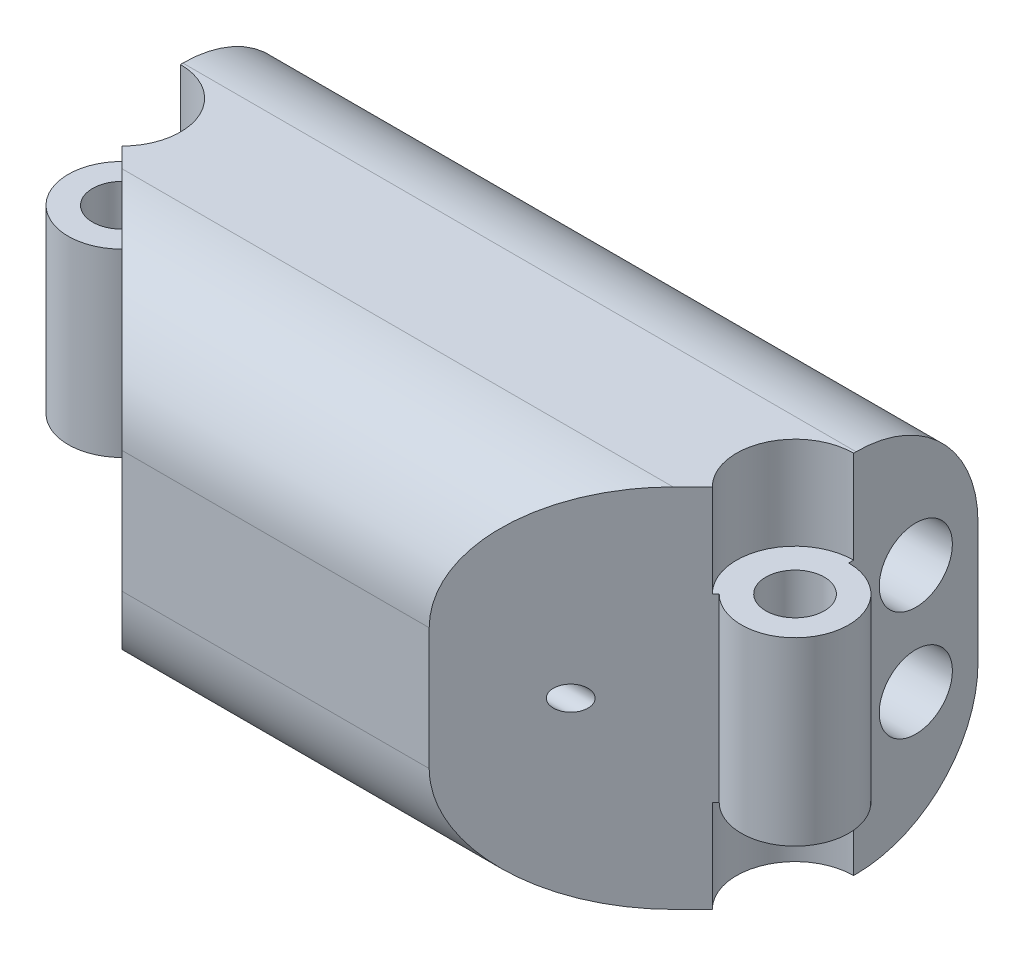
SolidWorks part; units mm, degrees
ref_plane "Front Plane" through (0, 0, 0) normal (1, 0, 0) x (0, 1, 0)
ref_plane "Top Plane" through (0, 0, 0) normal (0, 0, 1) x (0, 1, 0)
ref_plane "Right Plane" through (0, 0, 0) normal (0, 1, 0) x (-1, 0, 0)
sketch "Sketch1" plane through (0, 0, 0) normal (0, 1, 0) x (-1, 0, 0)
  line L1 (-6.3, 7.5) -> (6.3, 7.5)
  line L4 (13.8, -7.5) -> (-13.8, -7.5)
  line L6 (-13.8, -7.5) -> (-13.8, 0)
  line L7 (-13.8, 7.5) -> (-6.3, 7.5) construction
  line L8 (6.3, 7.5) -> (13.8, 7.5) construction
  line L9 (6.3, 7.5) -> (13.8, 0)
  line L10 (-13.8, 7.5) -> (13.8, -7.5) construction
  line L11 (-13.8, 0) -> (-6.3, 7.5)
  line L12 (-13.8, 7.5) -> (-13.8, 0) construction
  line L13 (13.8, 0) -> (13.8, -7.5)
  line L14 (13.8, 0) -> (13.8, 7.5) construction
  arc A4 (12.1029, 1.6971) -> (13.8, -2.4) centre (13.8, 0) ccw
  circle A5 centre (13.8, 0) radius 1.2 construction
  circle A6 centre (13.8, 0) radius 2.2 construction
  arc A7 (-13.8, -2.4) -> (-12.1029, 1.6971) centre (-13.8, 0) ccw
  dimension "D3" = 1
  dimension "D4" = 0.2
  dimension "D5" = 4.8
  dimension "D2" = 2.4
  dimension "D1" = 15
extrude "Boss-Extrude1" add sketch "Sketch1" along normal blind 7.5 and the other way blind 7.5 contours L1 L4 region at (0, 0, -0.7982)
sketch "Sketch5" plane through (13.8, 0, 0) normal (1, 0, 0) x (0, 1, 0)
  line L0 (0, -2.4) -> (0, -7.5) construction
  line L1 (-2.25, -4.95) -> (2.25, -4.95) construction
  line L2 (-7.5, -2.4) -> (7.5, -2.4) construction
  line L3 (-7.5, -7.5) -> (7.5, -7.5) construction
  circle A0 centre (-2.25, -4.95) radius 1.5
  circle A1 centre (2.25, -4.95) radius 1.5
  point P4 (0.75, -4.95)
  point P7 (0, -4.95)
  point P8 (-0.75, -4.95)
  point P9 (0, -4.95)
  dimension "D1" = 3
  dimension "D2" = 1.5
  dimension "D3" = 0
extrude "Cut-Extrude3" cut sketch "Sketch5" against normal up to next
fillet "Fillet1" radius 5 2 edges at (0, -7.5, -7.5) (0, 7.5, -7.5)
sketch "Sketch3" plane through (0, 0, 0) normal (1, 0, 0) x (0, 1, 0)
  line L0 (-7.5, 4.5985) -> (7.5, 4.5985) construction
  line L3 (-7.5, 1.6971) -> (-7.5, 7.5) construction
  line L4 (7.5, 1.6971) -> (7.5, 7.5) construction
  circle A0 centre (0, 4.5985) radius 0.5
extrude "Cut-Extrude2" cut sketch "Sketch3" against normal up to next and the other way up to next
fillet "Fillet2" radius 5 2 edges at (0, 7.5, 7.5) (0, -7.5, 7.5)
sketch "Sketch6" plane through (0, 0, 0) normal (0, 1, 0) x (-1, 0, 0)
  line L4 (0, 7.5) -> (0, -7.5) construction
  line L5 (-6.3, 7.5) -> (6.3, 7.5) construction
  line L6 (13.8, -7.5) -> (-13.8, -7.5) construction
  line L7 (-12.1029, 1.6971) -> (-12.2444, 1.5556)
  line L9 (-13.8, -2.4) -> (-13.8, -2.2)
  line L10 (-12.1029, 1.6971) -> (-11.3, 2.5) construction
  line L11 (13.8, -2.4) -> (13.8, -2.2)
  line L12 (12.1029, 1.6971) -> (12.2444, 1.5556)
  arc A6 (-12.2444, 1.5556) -> (-13.8, -2.2) centre (-13.8, 0) ccw
  circle A7 centre (-13.8, 0) radius 1.2
  arc A8 (-13.8, -2.4) -> (-12.1029, 1.6971) centre (-13.8, 0) ccw
  arc A9 (-13.8, -2.4) -> (-12.1029, 1.6971) centre (-13.8, 0) ccw construction
  arc A10 (13.8, -2.4) -> (12.1029, 1.6971) centre (13.8, 0) cw
  circle A11 centre (13.8, 0) radius 1.2
  arc A12 (12.2444, 1.5556) -> (13.8, -2.2) centre (13.8, 0) cw
  dimension "D1" = 0.2
  dimension "D2" = 1
extrude "Boss-Extrude2" add sketch "Sketch6" along normal blind 3.7 and the other way blind 3.7
